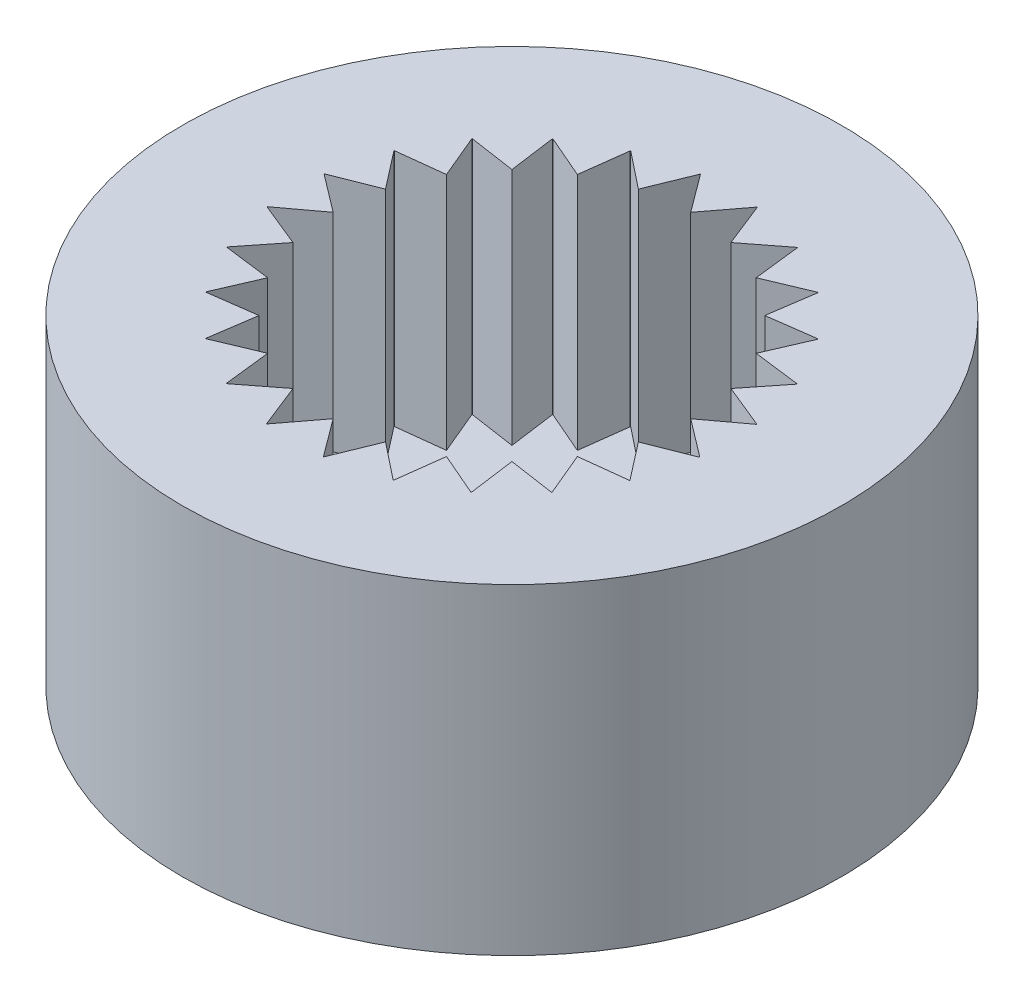
SolidWorks part; units mm, degrees
ref_plane "Front Plane" through (0, 0, 0) normal (0, 0, 1) x (1, 0, 0)
ref_plane "Top Plane" through (0, 0, 0) normal (0, 1, 0) x (1, 0, 0)
ref_plane "Right Plane" through (0, 0, 0) normal (1, 0, 0) x (0, 0, -1)
sketch "Sketch1" plane through (0, 0, 0) normal (0, 1, 0) x (1, 0, 0)
  line L0 (0, 2.65) -> (0, 2.17) construction
  line L1 (-0.34, 2.6281) -> (0, 2.17)
  line L2 (0, 2.17) -> (0.3473, 2.6271)
  line L3 (0.5616, 2.0961) -> (1.0154, 2.4477)
  line L4 (0.3518, 2.6265) -> (0.5616, 2.0961)
  line L5 (1.085, 1.8793) -> (1.6143, 2.1015)
  line L6 (1.0196, 2.446) -> (1.085, 1.8793)
  line L7 (1.5344, 1.5344) -> (2.1032, 1.6121)
  line L8 (1.6179, 2.0988) -> (1.5344, 1.5344)
  line L9 (1.8793, 1.085) -> (2.4488, 1.0128)
  line L10 (2.106, 1.6085) -> (1.8793, 1.085)
  line L11 (2.0961, 0.5616) -> (2.6275, 0.3445)
  line L12 (2.4505, 1.0086) -> (2.0961, 0.5616)
  line L13 (2.17, 0) -> (2.6271, -0.3473)
  line L14 (2.6281, 0.34) -> (2.17, 0)
  line L15 (2.0961, -0.5616) -> (2.4477, -1.0154)
  line L16 (2.6265, -0.3518) -> (2.0961, -0.5616)
  line L17 (1.8793, -1.085) -> (2.1015, -1.6143)
  line L18 (2.446, -1.0196) -> (1.8793, -1.085)
  line L19 (1.5344, -1.5344) -> (1.6121, -2.1032)
  line L20 (2.0988, -1.6179) -> (1.5344, -1.5344)
  line L21 (1.085, -1.8793) -> (1.0128, -2.4488)
  line L22 (1.6085, -2.106) -> (1.085, -1.8793)
  line L23 (0.5616, -2.0961) -> (0.3445, -2.6275)
  line L24 (1.0086, -2.4505) -> (0.5616, -2.0961)
  line L25 (0, -2.17) -> (-0.3473, -2.6271)
  line L26 (0.34, -2.6281) -> (0, -2.17)
  line L27 (-0.5616, -2.0961) -> (-1.0154, -2.4477)
  line L28 (-0.3518, -2.6265) -> (-0.5616, -2.0961)
  line L29 (-1.085, -1.8793) -> (-1.6143, -2.1015)
  line L30 (-1.0196, -2.446) -> (-1.085, -1.8793)
  line L31 (-1.5344, -1.5344) -> (-2.1032, -1.6121)
  line L32 (-1.6179, -2.0988) -> (-1.5344, -1.5344)
  line L33 (-1.8793, -1.085) -> (-2.4488, -1.0128)
  line L34 (-2.106, -1.6085) -> (-1.8793, -1.085)
  line L35 (-2.0961, -0.5616) -> (-2.6275, -0.3445)
  line L36 (-2.4505, -1.0086) -> (-2.0961, -0.5616)
  line L37 (-2.17, 0) -> (-2.6271, 0.3473)
  line L38 (-2.6281, -0.34) -> (-2.17, 0)
  line L39 (-2.0961, 0.5616) -> (-2.4477, 1.0154)
  line L40 (-2.6265, 0.3518) -> (-2.0961, 0.5616)
  line L41 (-1.8793, 1.085) -> (-2.1015, 1.6143)
  line L42 (-2.446, 1.0196) -> (-1.8793, 1.085)
  line L43 (-1.5344, 1.5344) -> (-1.6121, 2.1032)
  line L44 (-2.0988, 1.6179) -> (-1.5344, 1.5344)
  line L45 (-1.085, 1.8793) -> (-1.0128, 2.4488)
  line L46 (-1.6085, 2.106) -> (-1.085, 1.8793)
  line L47 (-0.5616, 2.0961) -> (-0.3445, 2.6275)
  line L48 (-1.0086, 2.4505) -> (-0.5616, 2.0961)
  circle A0 centre (0, 0) radius 4
  arc A1 (-1.0086, 2.4505) -> (-1.0128, 2.4488) centre (0, 0) ccw
  arc A2 (-1.6085, 2.106) -> (-1.6121, 2.1032) centre (0, 0) ccw
  arc A3 (-2.0988, 1.6179) -> (-2.1015, 1.6143) centre (0, 0) ccw
  arc A4 (-2.446, 1.0196) -> (-2.4477, 1.0154) centre (0, 0) ccw
  arc A5 (-2.6265, 0.3518) -> (-2.6271, 0.3473) centre (0, 0) ccw
  arc A6 (-2.6281, -0.34) -> (-2.6275, -0.3445) centre (0, 0) ccw
  arc A7 (-2.4505, -1.0086) -> (-2.4488, -1.0128) centre (0, 0) ccw
  arc A8 (-2.106, -1.6085) -> (-2.1032, -1.6121) centre (0, 0) ccw
  arc A9 (-1.6179, -2.0988) -> (-1.6143, -2.1015) centre (0, 0) ccw
  arc A10 (-1.0196, -2.446) -> (-1.0154, -2.4477) centre (0, 0) ccw
  arc A11 (-0.3518, -2.6265) -> (-0.3473, -2.6271) centre (0, 0) ccw
  arc A12 (0.34, -2.6281) -> (0.3445, -2.6275) centre (0, 0) ccw
  arc A13 (1.0086, -2.4505) -> (1.0128, -2.4488) centre (0, 0) ccw
  arc A14 (1.6085, -2.106) -> (1.6121, -2.1032) centre (0, 0) ccw
  arc A15 (2.0988, -1.6179) -> (2.1015, -1.6143) centre (0, 0) ccw
  arc A16 (2.446, -1.0196) -> (2.4477, -1.0154) centre (0, 0) ccw
  arc A17 (2.6265, -0.3518) -> (2.6271, -0.3473) centre (0, 0) ccw
  arc A18 (2.6281, 0.34) -> (2.6275, 0.3445) centre (0, 0) ccw
  arc A19 (2.4505, 1.0086) -> (2.4488, 1.0128) centre (0, 0) ccw
  arc A20 (2.106, 1.6085) -> (2.1032, 1.6121) centre (0, 0) ccw
  arc A21 (1.6179, 2.0988) -> (1.6143, 2.1015) centre (0, 0) ccw
  arc A22 (1.0196, 2.446) -> (1.0154, 2.4477) centre (0, 0) ccw
  arc A23 (0.3518, 2.6265) -> (0.3473, 2.6271) centre (0, 0) ccw
  arc A24 (-0.34, 2.6281) -> (-0.3445, 2.6275) centre (0, 0) ccw
  point P6 (-0.34, 2.6281)
  point P7 (0.3473, 2.6271)
  point P82 (0, 0)
  dimension "D1" = 8
  dimension "D2" = 5.3
  dimension "D3" = 0.48
  dimension "D4" = 0.34
  dimension "D5" = 0.3473
  dimension "D6" = 24
extrude "Boss-Extrude7" add sketch "Sketch1" along normal blind 1 contours L1 A24 L47 L48 A1 L45 L46 A2 L43 L44 A3 L41 L42 A4 L39 L40 A5 L37 L38 A6 L35 L36 A7 L33 L34 A8 L31 L32 A9 L29 L30 A10 L27 L28 A11 L25 L26 A12 L23 L24 A13 L21 L22 A14 L19 L20 A15 L17 L18 A16 L15 | A0 A24 L1 L2 A23 L4 L3 A22 L6 L5 A21 L8 L7 A20 L10 L9 A19 L12 L11 A18 L14 L13 A17 L16 L15 A16 L18 L17 A15 L20 L19 A14 L22 L21 A13 L24 L23 A12 L26 L25 A11 L28 L27 A10 L30 L29 A9 L32 region at (0, 0, 0) region at (-3.8869, 0, 0)
extrude "Boss-Extrude8" add sketch "Sketch1<4>" along normal blind 2.9 from surface starting at face at (0, 1, 4)
sketch "Sketch1<4>" plane through (0, 0, 0) normal (0, 1, 0) x (1, 0, 0) same geometry as "Sketch1"
